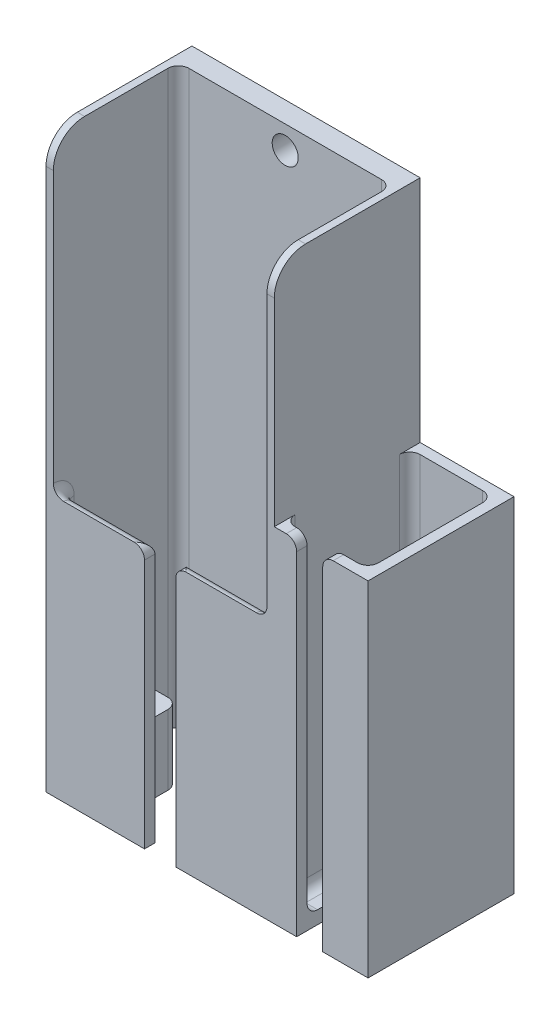
SolidWorks part; units mm, degrees
ref_plane "Front Plane" through (0, 0, 0) normal (0, 0, 1) x (1, 0, 0)
ref_plane "Top Plane" through (0, 0, 0) normal (0, 1, 0) x (1, 0, 0)
ref_plane "Right Plane" through (0, 0, 0) normal (1, 0, 0) x (0, 0, -1)
sketch "Sketch1" plane through (0, 0, 0) normal (0, 0, 1) x (1, 0, 0)
  line L1 (0, 0) -> (55.626, 0)
  line L2 (0, 0) -> (0, -139.7)
  line L3 (0, -139.7) -> (55.626, -139.7)
  line L4 (55.626, 0) -> (55.626, -139.7)
  dimension "D1" = 55.626
  dimension "D2" = 139.7
extrude "Boss-Extrude1" add sketch "Sketch1" along normal blind 35.56
ref_plane "Plane1" through (0, 0, 5.08) normal (0, 0, -1) x (-1, 0, 0)
sketch "Sketch2" plane through (0, 0, 5.08) normal (0, 0, -1) x (-1, 0, 0)
  line L1 (-1.778, -33.02) -> (-53.848, -33.02)
  line L2 (-1.778, -33.02) -> (-1.778, -122.6312)
  line L3 (-1.778, -122.6312) -> (-14.478, -122.6312)
  line L4 (-53.848, -33.02) -> (-53.848, -122.6312)
  line L5 (-1.778, -33.02) -> (-53.848, -122.6312) construction
  line L6 (-1.778, -122.6312) -> (-53.848, -33.02) construction
  line L8 (-55.626, 0) -> (0, 0) construction
  line L10 (0, -139.7) -> (-55.626, -139.7) construction
  line L11 (-14.478, -139.7) -> (-41.148, -139.7)
  line L12 (-14.478, -139.7) -> (-14.478, -122.6312)
  line L14 (-41.148, -139.7) -> (-41.148, -122.6312)
  line L15 (-14.478, -139.7) -> (-41.148, -122.6312) construction
  line L16 (-14.478, -122.6312) -> (-41.148, -139.7) construction
  line L17 (-41.148, -122.6312) -> (-53.848, -122.6312)
  point P0 (-27.813, -77.8256)
  point P13 (-27.813, 0)
  point P14 (-27.813, -131.1656)
  dimension "D1" = 17.0688
  dimension "D2" = 106.68
  dimension "D3" = 52.07
  dimension "D4" = 26.67
extrude "Cut-Extrude1" cut sketch "Sketch2" against normal blind 27.94
sketch "Sketch3" plane through (0, 0, 35.56) normal (0, 0, 1) x (1, 0, 0)
  line L0 (24.003, -139.7) -> (31.623, -139.7)
  line L1 (0, -139.7) -> (55.626, -139.7) construction
  line L2 (31.623, -139.7) -> (31.623, -76.2)
  line L3 (31.623, -76.2) -> (53.848, -76.2)
  line L4 (53.848, 0) -> (1.778, 0)
  line L7 (1.778, 0) -> (1.778, -76.2)
  line L8 (1.778, -76.2) -> (24.003, -76.2)
  line L9 (24.003, -76.2) -> (24.003, -139.7)
  line L11 (53.848, -76.2) -> (53.848, 0)
  line L12 (55.626, 0) -> (0, 0) construction
  line L13 (1.778, -122.6312) -> (1.778, -33.02) construction
  line L14 (53.848, -33.02) -> (53.848, -122.6312) construction
  point P5 (27.813, -139.7)
  point P16 (27.813, -139.7)
  dimension "D1" = 7.62
  dimension "D2" = 63.5
extrude "Cut-Extrude6" cut sketch "Sketch3" against normal blind 30.48
sketch "Sketch4" plane through (0, 0, 0) normal (0, 0, -1) x (-1, 0, 0)
  line L0 (-55.626, 0) -> (0, 0) construction
  line L1 (-53.848, 0) -> (-1.778, 0) construction
  circle A0 centre (-27.813, -5.588) radius 3.175
  point P4 (-27.813, 0)
  dimension "D1" = 6.35
  dimension "D2" = 5.588
extrude "Cut-Extrude7" cut sketch "Sketch4" against normal through all
sketch "Sketch5" plane through (0, -122.6312, 0) normal (0, 1, 0) x (1, 0, 0)
  line L0 (14.478, -33.02) -> (14.478, -5.08) construction
  line L1 (1.778, -5.08) -> (14.478, -5.08)
  line L2 (1.778, -5.08) -> (1.778, -17.78)
  line L3 (1.778, -17.78) -> (14.478, -17.78)
  line L4 (14.478, -5.08) -> (14.478, -17.78)
  line L5 (41.148, -33.02) -> (41.148, -5.08) construction
  line L6 (53.848, -33.02) -> (41.148, -33.02)
  line L7 (53.848, -33.02) -> (53.848, -20.32)
  line L8 (53.848, -20.32) -> (41.148, -20.32)
  line L9 (41.148, -33.02) -> (41.148, -20.32)
  dimension "D1" = 12.7
extrude "Cut-Extrude8" cut sketch "Sketch5" against normal through all
sketch "Sketch6" plane through (0, -139.7, 0) normal (0, -1, 0) x (1, 0, 0)
  line L0 (55.626, 35.56) -> (53.848, 35.56) construction
  line L1 (55.626, 0) -> (78.486, 0)
  line L3 (55.626, 35.56) -> (78.486, 35.56)
  line L4 (78.486, 0) -> (78.486, 35.56)
  line L5 (55.626, 35.56) -> (55.626, 33.02)
  line L6 (55.626, 2.54) -> (75.946, 2.54)
  line L8 (55.626, 33.02) -> (75.946, 33.02)
  line L9 (75.946, 2.54) -> (75.946, 33.02)
  line L10 (55.626, 0) -> (55.626, 2.54)
  line L12 (55.626, 35.56) -> (55.626, 0) construction
  dimension "D1" = 20.32
  dimension "D2" = 2.54
  dimension "D3" = 2.54
  dimension "D4" = 2.54
extrude "Boss-Extrude2" add sketch "Sketch6" against normal blind 83.82
sketch "Sketch7" plane through (0, -139.7, 0) normal (0, -1, 0) x (1, 0, 0)
  line L0 (55.626, 33.02) -> (75.946, 33.02) construction
  line L1 (55.626, 33.02) -> (75.946, 33.02)
  line L2 (55.626, 33.02) -> (55.626, 2.54)
  line L3 (55.626, 2.54) -> (75.946, 2.54)
  line L4 (75.946, 33.02) -> (75.946, 2.54)
  line L5 (55.626, 33.02) -> (55.626, 2.54) construction
  circle A0 centre (64.262, 17.78) radius 6.35
  point P11 (0, 0)
  point P12 (0, 0)
  point P13 (0, 0)
  point P14 (0, 0)
  point P15 (55.626, 17.78)
  dimension "D1" = 12.7
  dimension "D2" = 8.636
extrude "Boss-Extrude3" add sketch "Sketch7" against normal blind 3.175
sketch "Sketch8" plane through (0, 0, 35.56) normal (0, 0, 1) x (1, 0, 0)
  line L0 (78.486, -55.88) -> (55.626, -55.88) construction
  line L1 (61.087, -55.88) -> (67.437, -55.88)
  line L2 (61.087, -55.88) -> (61.087, -139.7)
  line L3 (61.087, -139.7) -> (67.437, -139.7)
  line L4 (67.437, -55.88) -> (67.437, -139.7)
  line L5 (31.623, -139.7) -> (78.486, -139.7) construction
  line L7 (55.626, -55.88) -> (55.626, 0) construction
  point P13 (64.262, -55.88)
  dimension "D1" = 6.35
  dimension "D2" = 8.636
extrude "Cut-Extrude9" cut sketch "Sketch8" against normal blind 17.78
fillet "Fillet1" radius 7.62 6 edges at (14.478, -131.1656, 33.02) (41.148, -131.1656, 5.08) (54.737, 0, 35.56) (0.889, 0, 35.56) (67.437, -138.1125, 23.2793) (61.087, -138.1125, 23.2793)
fillet "Fillet2" radius 2.54 27 edges at (11.938, -122.6312, 33.02) (1.778, -122.6312, 25.4) (53.848, -131.1656, 20.32) (53.848, -122.6312, 12.7) (43.688, -122.6312, 5.08) (1.778, -99.4156, 33.02) (24.003, -76.2, 34.29) (31.623, -76.2, 34.29) (12.8905, -76.2, 33.02) (42.7355, -76.2, 33.02) (14.478, -131.1656, 17.78) (41.148, -131.1656, 20.32) (53.848, -107.95, 33.02) (1.778, -131.1656, 17.78) (53.848, -61.3156, 5.08) (1.778, -69.85, 5.08) (65.786, -136.525, 2.54) (75.946, -136.525, 17.78) (71.6915, -136.525, 33.02) (58.3565, -136.525, 33.02) (55.626, -136.525, 17.78) (75.946, -96.2025, 33.02) (55.626, -96.2025, 33.02) (55.626, -96.2025, 2.54) (75.946, -96.2025, 2.54) (67.437, -55.88, 34.29) (61.087, -55.88, 34.29)
